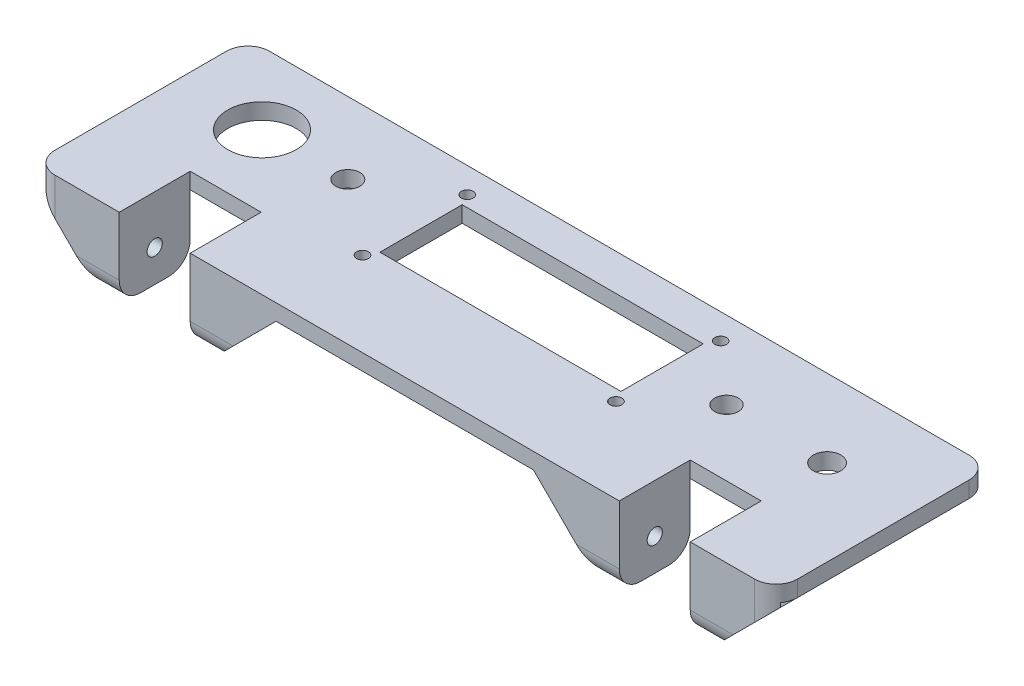
SolidWorks part; units mm, degrees
ref_plane "Front Plane" through (0, 0, 0) normal (0, 0, 1) x (1, 0, 0)
ref_plane "Top Plane" through (0, 0, 0) normal (0, 1, 0) x (1, 0, 0)
ref_plane "Right Plane" through (0, 0, 0) normal (1, 0, 0) x (0, 0, -1)
sketch "Sketch2" plane through (0, 0, 0) normal (0, 1, 0) x (1, 0, 0)
  line L0 (-109.9, 0) -> (109.9, 0)
  line L1 (109.9, 0) -> (109.9, -63.5)
  line L2 (109.9, -63.5) -> (84.5, -63.5)
  line L3 (84.5, -63.5) -> (84.5, -42.5)
  line L4 (84.5, -42.5) -> (63.5, -42.5)
  line L5 (63.5, -42.5) -> (63.5, -63.5)
  line L6 (63.5, -63.5) -> (-63.5, -63.5)
  line L7 (0, 0) -> (0, -108.2183) construction
  line L8 (-109.9, 0) -> (-109.9, -63.5)
  line L9 (-109.9, -63.5) -> (-84.5, -63.5)
  line L10 (-84.5, -63.5) -> (-84.5, -42.5)
  line L11 (-84.5, -42.5) -> (-63.5, -42.5)
  line L12 (-63.5, -42.5) -> (-63.5, -63.5)
  point P16 (0, -63.5)
  dimension "D1" = 25.4
  dimension "D2" = 21
  dimension "D3" = 21
  dimension "D4" = 21
  dimension "D5" = 63.5
  dimension "D6" = 127
extrude "Boss-Extrude1" add sketch "Sketch2" along normal blind 4.7625
sketch "Sketch3" plane through (0, 4.7625, 0) normal (0, 1, 0) x (1, 0, 0)
  line L0 (0, 0) -> (0, -79.7271) construction
  line L1 (-40, -41) -> (40, -41) construction
  line L2 (-40, -41) -> (-40, -5) construction
  line L3 (-40, -5) -> (40, -5) construction
  line L4 (40, -41) -> (40, -5) construction
  line L5 (-40, -41) -> (40, -5) construction
  line L6 (-40, -5) -> (40, -41) construction
  line L7 (109.9, 0) -> (-109.9, 0) construction
  line L8 (-37.5, -7.5) -> (-37.5, -38.5) construction
  line L9 (-37.5, -23) -> (35.675, -23) construction
  line L10 (-63.5, 0) -> (-63.5, -42.5) construction
  line L15 (-84.5, -42.5) -> (-63.5, -42.5) construction
  line L16 (-109.9, -21.25) -> (-59.1, -21.25) construction
  line L17 (-109.9, 0) -> (-109.9, -63.5) construction
  line L18 (35.675, -23) -> (109.9, -23) construction
  line L19 (-35.675, -35.175) -> (35.675, -35.175)
  line L20 (-35.675, -35.175) -> (-35.675, -10.825)
  line L21 (-35.675, -10.825) -> (35.675, -10.825)
  line L22 (35.675, -35.175) -> (35.675, -10.825)
  line L23 (-35.675, -35.175) -> (35.675, -10.825) construction
  line L24 (-35.675, -10.825) -> (35.675, -35.175) construction
  line L25 (109.9, -63.5) -> (109.9, 0) construction
  circle A0 centre (-84.5, -21.25) radius 10.16
  circle A1 centre (-59.1, -21.25) radius 3.556
  circle A2 centre (-37.5, -38.5) radius 1.75
  circle A3 centre (-37.5, -7.5) radius 1.75
  circle A4 centre (37.5, -38.5) radius 1.75
  circle A5 centre (37.5, -7.5) radius 1.75
  circle A6 centre (54.725, -23) radius 3.4925
  circle A7 centre (84.5, -23) radius 4.064
  point P4 (0, -23)
  point P23 (0, -23)
  point P32 (-63.5, -21.25)
  dimension "D1" = 20.32
  dimension "D2" = 7.112
  dimension "D7" = 3.5
  dimension "D8" = 3.5
  dimension "D15" = 6.985
  dimension "D12" = 8.128
  dimension "D3" = 80
  dimension "D4" = 36
  dimension "D5" = 5
  dimension "D6" = 31
  dimension "D9" = 75
  dimension "D10" = 71.35
  dimension "D11" = 24.35
  dimension "D13" = 25.4
  dimension "D14" = 25.4
  dimension "D16" = 19.05
  dimension "D17" = 25.4
extrude "Cut-Extrude1" cut sketch "Sketch3" against normal up to next
sketch "Sketch4" plane through (0, 0, 0) normal (0, -1, 0) x (1, 0, 0)
  line L0 (-84.5, 42.5) -> (-63.5, 42.5) construction
  line L1 (-84.5, 63.5) -> (-90.85, 63.5)
  line L2 (-84.5, 63.5) -> (-84.5, 42.5)
  line L3 (-84.5, 42.5) -> (-90.85, 42.5)
  line L4 (-90.85, 63.5) -> (-90.85, 42.5)
  line L5 (0, 63.5) -> (0, -75.9267) construction
  line L6 (-63.5, 63.5) -> (63.5, 63.5) construction
  line L7 (84.5, 42.5) -> (90.85, 42.5)
  line L8 (90.85, 63.5) -> (90.85, 42.5)
  line L9 (84.5, 63.5) -> (90.85, 63.5)
  line L10 (84.5, 63.5) -> (84.5, 42.5)
  line L11 (-74, 42.5) -> (-74, 70.4389) construction
  line L12 (-63.5, 42.5) -> (-57.15, 42.5)
  line L13 (-57.15, 63.5) -> (-57.15, 42.5)
  line L14 (-63.5, 63.5) -> (-57.15, 63.5)
  line L15 (-63.5, 63.5) -> (-63.5, 42.5)
  line L16 (63.5, 63.5) -> (63.5, 42.5)
  line L17 (63.5, 63.5) -> (57.15, 63.5)
  line L18 (57.15, 63.5) -> (57.15, 42.5)
  line L19 (63.5, 42.5) -> (57.15, 42.5)
  dimension "D1" = 6.35
extrude "Boss-Extrude2" add sketch "Sketch4" along normal blind 19.05
sketch "Sketch5" plane through (90.85, 0, 0) normal (1, 0, 0) x (0, 0, -1)
  line L0 (-42.5, -19.05) -> (-63.5, -19.05) construction
  line L1 (-53, -9.525) -> (-53, -19.05) construction
  circle A0 centre (-53, -9.525) radius 2.25
  dimension "D1" = 4.5
  dimension "D2" = 9.525
extrude "Cut-Extrude2" cut sketch "Sketch5" against normal through all
sketch "Sketch6" plane through (0, 0, 63.5) normal (0, 0, 1) x (1, 0, 0)
  line L0 (90.85, -19.05) -> (109.9, 0)
  line L1 (109.9, 0) -> (90.85, 0)
  line L2 (90.85, 0) -> (90.85, -19.05)
  line L3 (57.15, -19.05) -> (38.1, 0)
  line L4 (-57.15, 0) -> (57.15, 0) construction
  line L5 (38.1, 0) -> (57.15, 0)
  line L6 (57.15, 0) -> (57.15, -19.05)
  line L7 (-90.85, -19.05) -> (-90.85, 0)
  line L8 (-90.85, 0) -> (-109.9, 0)
  line L9 (-109.9, 0) -> (-90.85, -19.05)
  line L10 (-57.15, -19.05) -> (-57.15, 0)
  line L11 (-57.15, 0) -> (-38.1, 0)
  line L12 (-38.1, 0) -> (-57.15, -19.05)
extrude "Boss-Extrude3" add sketch "Sketch6" against normal blind 2.54
sketch "Sketch7" plane through (0, 0, 42.5) normal (0, 0, -1) x (-1, 0, 0)
  line L0 (-90.85, -19.05) -> (-90.85, 0)
  line L1 (-90.85, 0) -> (-109.9, 0)
  line L2 (-109.9, 0) -> (-90.85, -19.05)
  line L3 (-57.15, 0) -> (-38.1, 0)
  line L4 (-38.1, 0) -> (-57.15, -19.05)
  line L5 (-57.15, -19.05) -> (-57.15, 0)
  line L6 (57.15, 0) -> (57.15, -19.05)
  line L7 (57.15, -19.05) -> (38.1, 0)
  line L8 (38.1, 0) -> (57.15, 0)
  line L9 (90.85, 0) -> (90.85, -19.05)
  line L10 (90.85, -19.05) -> (109.9, 0)
  line L11 (109.9, 0) -> (90.85, 0)
extrude "Boss-Extrude4" add sketch "Sketch7" against normal blind 2.54
fillet "Fillet1" radius 6.35 12 edges at (109.9, 2.3813, 0) (109.9, 2.3813, 63.5) (87.675, -19.05, 63.5) (87.675, -19.05, 42.5) (60.325, -19.05, 42.5) (60.325, -19.05, 63.5) (-109.9, 2.3813, 0) (-60.325, -19.05, 63.5) (-60.325, -19.05, 42.5) (-87.675, -19.05, 42.5) (-87.675, -19.05, 63.5) (-109.9, 2.3813, 63.5)
